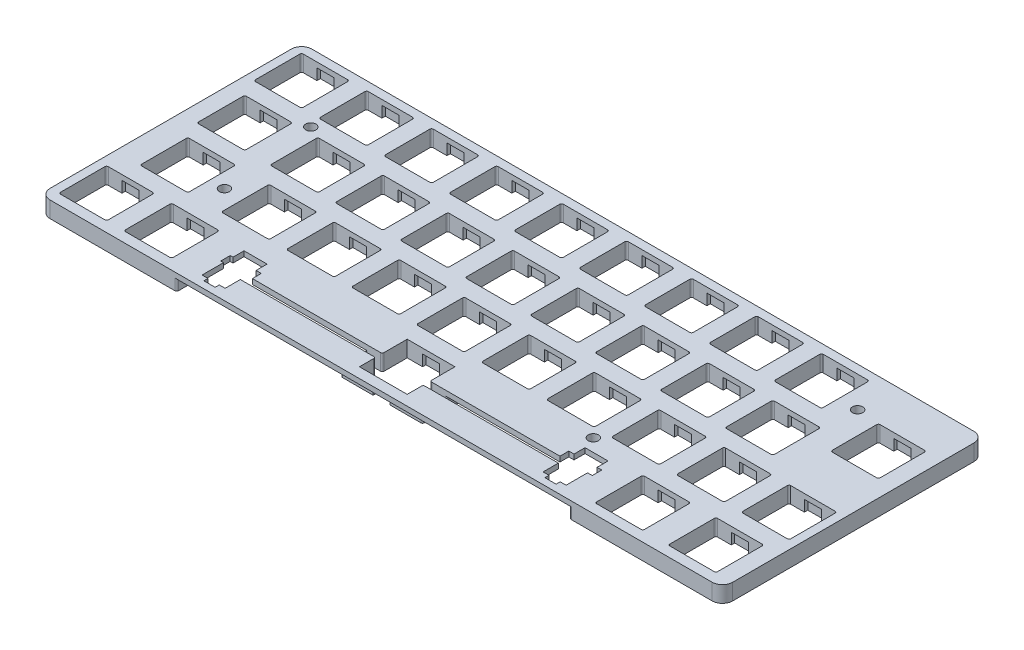
SolidWorks part; units mm, degrees
ref_plane "Front Plane" through (0, 0, 0) normal (0, 0, 1) x (1, 0, 0)
ref_plane "Top Plane" through (0, 0, 0) normal (0, 1, 0) x (1, 0, 0)
ref_plane "Right Plane" through (0, 0, 0) normal (1, 0, 0) x (0, 0, -1)
sketch "Sketch1" plane through (0, 0, 0) normal (0, 1, 0) x (1, 0, 0)
  line L0 (-2.525, 73.675) -> (197.5, 73.675)
  line L1 (-2.525, 73.675) -> (-2.525, -3)
  line L2 (197.5, 73.675) -> (197.5, -3)
  line L3 (-2.525, -3) -> (197.5, -3)
  line L5 (102.1062, 14) -> (88.1063, 14)
  line L6 (102.1062, 0) -> (88.1063, 0)
  line L8 (88.1063, 14) -> (88.1063, 9.3)
  line L9 (88.1063, 9.3) -> (48.5063, 9.3)
  line L10 (48.5063, 9.3) -> (48.5063, 12.53)
  line L11 (48.5063, 12.53) -> (41.7563, 12.53)
  line L12 (41.7563, 12.53) -> (41.7563, 9.3)
  line L13 (41.7563, 9.3) -> (40.9313, 9.3)
  line L14 (40.9313, 9.3) -> (40.9313, 6.515)
  line L15 (40.9313, 6.515) -> (41.7563, 6.515)
  line L16 (41.7563, 6.515) -> (41.7563, 0.23)
  line L17 (41.7563, 0.23) -> (43.4812, 0.23)
  line L18 (43.4812, 0.23) -> (43.4812, -0.97)
  line L19 (43.4812, -0.97) -> (46.7812, -0.97)
  line L20 (46.7812, -0.97) -> (46.7812, 0.23)
  line L21 (46.7812, 0.23) -> (48.5062, 0.23)
  line L22 (48.5062, 0.23) -> (48.5062, 4.7)
  line L23 (48.5062, 4.7) -> (88.1063, 4.7)
  line L24 (88.1063, 4.7) -> (88.1063, 0)
  line L25 (102.1062, 0) -> (102.1062, 4.7)
  line L26 (102.1062, 4.7) -> (141.7063, 4.7)
  line L27 (141.7063, 4.7) -> (141.7063, 0.23)
  line L28 (141.7063, 0.23) -> (143.4313, 0.23)
  line L29 (143.4313, 0.23) -> (143.4313, -0.97)
  line L30 (143.4313, -0.97) -> (146.7313, -0.97)
  line L31 (146.7313, -0.97) -> (146.7313, 0.23)
  line L32 (146.7313, 0.23) -> (148.4563, 0.23)
  line L33 (148.4563, 0.23) -> (148.4563, 6.515)
  line L34 (148.4563, 6.515) -> (149.8378, 6.515)
  line L35 (149.8378, 6.515) -> (149.8378, 9.3)
  line L36 (149.8378, 9.3) -> (148.4563, 9.3)
  line L37 (148.4563, 9.3) -> (148.4563, 12.53)
  line L38 (148.4563, 12.53) -> (141.7063, 12.53)
  line L39 (141.7063, 12.53) -> (141.7063, 9.3)
  line L40 (141.7063, 9.3) -> (102.1062, 9.3)
  line L41 (102.1062, 9.3) -> (102.1062, 14)
  line L42 (88.1063, 9.3) -> (88.1063, 6.7)
  line L43 (50.0312, 9.3) -> (140.1813, 9.3)
  line L44 (50.0312, 9.3) -> (50.0312, 6.7)
  line L45 (50.0312, 6.7) -> (140.1813, 6.7)
  line L46 (140.1813, 9.3) -> (140.1813, 6.7)
  line L47 (102.1062, 9.3) -> (102.1062, 6.7)
  point P0 (0, 64.15)
  line B0 (13.5, 71.15) -> (0.5, 71.15)
  line B1 (194.975, 19.55) -> (194.975, 32.55)
  line B2 (88.6062, 0) -> (101.6062, 0)
  line B3 (101.6062, 14) -> (88.6062, 14)
  line B4 (0.5, 57.15) -> (13.5, 57.15)
  line B5 (14, 57.65) -> (14, 70.65)
  line B6 (0, 70.65) -> (0, 57.65)
  line B7 (19.55, 57.15) -> (32.55, 57.15)
  line B8 (32.55, 71.15) -> (19.55, 71.15)
  line B9 (33.05, 57.65) -> (33.05, 70.65)
  line B10 (19.05, 70.65) -> (19.05, 57.65)
  line B11 (38.6, 57.15) -> (51.6, 57.15)
  line B12 (51.6, 71.15) -> (38.6, 71.15)
  line B13 (52.1, 57.65) -> (52.1, 70.65)
  line B14 (38.1, 70.65) -> (38.1, 57.65)
  line B15 (57.65, 57.15) -> (70.65, 57.15)
  line B16 (70.65, 71.15) -> (57.65, 71.15)
  line B17 (71.15, 57.65) -> (71.15, 70.65)
  line B18 (57.15, 70.65) -> (57.15, 57.65)
  line B19 (76.7, 57.15) -> (89.7, 57.15)
  line B20 (89.7, 71.15) -> (76.7, 71.15)
  line B21 (90.2, 57.65) -> (90.2, 70.65)
  line B22 (76.2, 70.65) -> (76.2, 57.65)
  line B23 (95.75, 57.15) -> (108.75, 57.15)
  line B24 (108.75, 71.15) -> (95.75, 71.15)
  line B25 (109.25, 57.65) -> (109.25, 70.65)
  line B26 (95.25, 70.65) -> (95.25, 57.65)
  line B27 (114.8, 57.15) -> (127.8, 57.15)
  line B28 (127.8, 71.15) -> (114.8, 71.15)
  line B29 (128.3, 57.65) -> (128.3, 70.65)
  line B30 (114.3, 70.65) -> (114.3, 57.65)
  line B31 (133.85, 57.15) -> (146.85, 57.15)
  line B32 (146.85, 71.15) -> (133.85, 71.15)
  line B33 (147.35, 57.65) -> (147.35, 70.65)
  line B34 (133.35, 70.65) -> (133.35, 57.65)
  line B35 (152.9, 57.15) -> (165.9, 57.15)
  line B36 (165.9, 71.15) -> (152.9, 71.15)
  line B37 (166.4, 57.65) -> (166.4, 70.65)
  line B38 (152.4, 70.65) -> (152.4, 57.65)
  line B39 (179.0938, 47.625) -> (192.0938, 47.625)
  line B40 (192.0938, 61.625) -> (179.0938, 61.625)
  line B41 (192.5938, 48.125) -> (192.5938, 61.125)
  line B42 (178.5938, 61.125) -> (178.5938, 48.125)
  line B43 (2.8813, 38.1) -> (15.8812, 38.1)
  line B44 (15.8812, 52.1) -> (2.8813, 52.1)
  line B45 (16.3813, 38.6) -> (16.3813, 51.6)
  line B46 (2.3813, 51.6) -> (2.3813, 38.6)
  line B47 (24.3125, 38.1) -> (37.3125, 38.1)
  line B48 (37.3125, 52.1) -> (24.3125, 52.1)
  line B49 (37.8125, 38.6) -> (37.8125, 51.6)
  line B50 (23.8125, 51.6) -> (23.8125, 38.6)
  line B51 (43.3625, 38.1) -> (56.3625, 38.1)
  line B52 (56.3625, 52.1) -> (43.3625, 52.1)
  line B53 (56.8625, 38.6) -> (56.8625, 51.6)
  line B54 (42.8625, 51.6) -> (42.8625, 38.6)
  line B55 (62.4125, 38.1) -> (75.4125, 38.1)
  line B56 (75.4125, 52.1) -> (62.4125, 52.1)
  line B57 (75.9125, 38.6) -> (75.9125, 51.6)
  line B58 (61.9125, 51.6) -> (61.9125, 38.6)
  line B59 (81.4625, 38.1) -> (94.4625, 38.1)
  line B60 (94.4625, 52.1) -> (81.4625, 52.1)
  line B61 (94.9625, 38.6) -> (94.9625, 51.6)
  line B62 (80.9625, 51.6) -> (80.9625, 38.6)
  line B63 (100.5125, 38.1) -> (113.5125, 38.1)
  line B64 (113.5125, 52.1) -> (100.5125, 52.1)
  line B65 (114.0125, 38.6) -> (114.0125, 51.6)
  line B66 (100.0125, 51.6) -> (100.0125, 38.6)
  line B67 (119.5625, 38.1) -> (132.5625, 38.1)
  line B68 (132.5625, 52.1) -> (119.5625, 52.1)
  line B69 (133.0625, 38.6) -> (133.0625, 51.6)
  line B70 (119.0625, 51.6) -> (119.0625, 38.6)
  line B71 (138.6125, 38.1) -> (151.6125, 38.1)
  line B72 (151.6125, 52.1) -> (138.6125, 52.1)
  line B73 (152.1125, 38.6) -> (152.1125, 51.6)
  line B74 (138.1125, 51.6) -> (138.1125, 38.6)
  line B75 (157.6625, 38.1) -> (170.6625, 38.1)
  line B76 (170.6625, 52.1) -> (157.6625, 52.1)
  line B77 (171.1625, 38.6) -> (171.1625, 51.6)
  line B78 (157.1625, 51.6) -> (157.1625, 38.6)
  line B79 (5.2625, 19.05) -> (18.2625, 19.05)
  line B80 (18.2625, 33.05) -> (5.2625, 33.05)
  line B81 (18.7625, 19.55) -> (18.7625, 32.55)
  line B82 (4.7625, 32.55) -> (4.7625, 19.55)
  line B83 (29.075, 19.05) -> (42.075, 19.05)
  line B84 (42.075, 33.05) -> (29.075, 33.05)
  line B85 (42.575, 19.55) -> (42.575, 32.55)
  line B86 (28.575, 32.55) -> (28.575, 19.55)
  line B87 (48.125, 19.05) -> (61.125, 19.05)
  line B88 (61.125, 33.05) -> (48.125, 33.05)
  line B89 (61.625, 19.55) -> (61.625, 32.55)
  line B90 (47.625, 32.55) -> (47.625, 19.55)
  line B91 (67.175, 19.05) -> (80.175, 19.05)
  line B92 (80.175, 33.05) -> (67.175, 33.05)
  line B93 (80.675, 19.55) -> (80.675, 32.55)
  line B94 (66.675, 32.55) -> (66.675, 19.55)
  line B95 (86.225, 19.05) -> (99.225, 19.05)
  line B96 (99.225, 33.05) -> (86.225, 33.05)
  line B97 (99.725, 19.55) -> (99.725, 32.55)
  line B98 (85.725, 32.55) -> (85.725, 19.55)
  line B99 (105.275, 19.05) -> (118.275, 19.05)
  line B100 (118.275, 33.05) -> (105.275, 33.05)
  line B101 (118.775, 19.55) -> (118.775, 32.55)
  line B102 (104.775, 32.55) -> (104.775, 19.55)
  line B103 (124.325, 19.05) -> (137.325, 19.05)
  line B104 (137.325, 33.05) -> (124.325, 33.05)
  line B105 (137.825, 19.55) -> (137.825, 32.55)
  line B106 (123.825, 32.55) -> (123.825, 19.55)
  line B107 (143.375, 19.05) -> (156.375, 19.05)
  line B108 (156.375, 33.05) -> (143.375, 33.05)
  line B109 (156.875, 19.55) -> (156.875, 32.55)
  line B110 (142.875, 32.55) -> (142.875, 19.55)
  line B111 (162.425, 19.05) -> (175.425, 19.05)
  line B112 (175.425, 33.05) -> (162.425, 33.05)
  line B113 (175.925, 19.55) -> (175.925, 32.55)
  line B114 (161.925, 32.55) -> (161.925, 19.55)
  line B115 (181.475, 19.05) -> (194.475, 19.05)
  line B116 (194.475, 33.05) -> (181.475, 33.05)
  line B117 (180.975, 32.55) -> (180.975, 19.55)
  line B118 (0.5, 0) -> (13.5, 0)
  line B119 (13.5, 14) -> (0.5, 14)
  line B120 (14, 0.5) -> (14, 13.5)
  line B121 (0, 13.5) -> (0, 0.5)
  line B122 (19.55, 0) -> (32.55, 0)
  line B123 (32.55, 14) -> (19.55, 14)
  line B124 (33.05, 0.5) -> (33.05, 13.5)
  line B125 (19.05, 13.5) -> (19.05, 0.5)
  line B126 (102.1062, 0.5) -> (102.1062, 13.5)
  line B127 (88.1063, 13.5) -> (88.1063, 0.5)
  line B128 (157.6625, 0) -> (170.6625, 0)
  line B129 (170.6625, 14) -> (157.6625, 14)
  line B130 (171.1625, 0.5) -> (171.1625, 13.5)
  line B131 (157.1625, 13.5) -> (157.1625, 0.5)
  line B132 (179.0938, 0) -> (192.0938, 0)
  line B133 (192.0938, 14) -> (179.0938, 14)
  line B134 (192.5938, 0.5) -> (192.5938, 13.5)
  line B135 (178.5938, 13.5) -> (178.5938, 0.5)
  arc B136 (0, 57.65) -> (0.5, 57.15) centre (0.5, 57.65) ccw
  arc B137 (13.5, 57.15) -> (14, 57.65) centre (13.5, 57.65) ccw
  arc B138 (14, 70.65) -> (13.5, 71.15) centre (13.5, 70.65) ccw
  arc B139 (0.5, 71.15) -> (0, 70.65) centre (0.5, 70.65) ccw
  arc B140 (19.05, 57.65) -> (19.55, 57.15) centre (19.55, 57.65) ccw
  arc B141 (32.55, 57.15) -> (33.05, 57.65) centre (32.55, 57.65) ccw
  arc B142 (33.05, 70.65) -> (32.55, 71.15) centre (32.55, 70.65) ccw
  arc B143 (19.55, 71.15) -> (19.05, 70.65) centre (19.55, 70.65) ccw
  arc B144 (38.1, 57.65) -> (38.6, 57.15) centre (38.6, 57.65) ccw
  arc B145 (51.6, 57.15) -> (52.1, 57.65) centre (51.6, 57.65) ccw
  arc B146 (52.1, 70.65) -> (51.6, 71.15) centre (51.6, 70.65) ccw
  arc B147 (38.6, 71.15) -> (38.1, 70.65) centre (38.6, 70.65) ccw
  arc B148 (57.15, 57.65) -> (57.65, 57.15) centre (57.65, 57.65) ccw
  arc B149 (70.65, 57.15) -> (71.15, 57.65) centre (70.65, 57.65) ccw
  arc B150 (71.15, 70.65) -> (70.65, 71.15) centre (70.65, 70.65) ccw
  arc B151 (57.65, 71.15) -> (57.15, 70.65) centre (57.65, 70.65) ccw
  arc B152 (76.2, 57.65) -> (76.7, 57.15) centre (76.7, 57.65) ccw
  arc B153 (89.7, 57.15) -> (90.2, 57.65) centre (89.7, 57.65) ccw
  arc B154 (90.2, 70.65) -> (89.7, 71.15) centre (89.7, 70.65) ccw
  arc B155 (76.7, 71.15) -> (76.2, 70.65) centre (76.7, 70.65) ccw
  arc B156 (95.25, 57.65) -> (95.75, 57.15) centre (95.75, 57.65) ccw
  arc B157 (108.75, 57.15) -> (109.25, 57.65) centre (108.75, 57.65) ccw
  arc B158 (109.25, 70.65) -> (108.75, 71.15) centre (108.75, 70.65) ccw
  arc B159 (95.75, 71.15) -> (95.25, 70.65) centre (95.75, 70.65) ccw
  arc B160 (114.3, 57.65) -> (114.8, 57.15) centre (114.8, 57.65) ccw
  arc B161 (127.8, 57.15) -> (128.3, 57.65) centre (127.8, 57.65) ccw
  arc B162 (128.3, 70.65) -> (127.8, 71.15) centre (127.8, 70.65) ccw
  arc B163 (114.8, 71.15) -> (114.3, 70.65) centre (114.8, 70.65) ccw
  arc B164 (133.35, 57.65) -> (133.85, 57.15) centre (133.85, 57.65) ccw
  arc B165 (146.85, 57.15) -> (147.35, 57.65) centre (146.85, 57.65) ccw
  arc B166 (147.35, 70.65) -> (146.85, 71.15) centre (146.85, 70.65) ccw
  arc B167 (133.85, 71.15) -> (133.35, 70.65) centre (133.85, 70.65) ccw
  arc B168 (152.4, 57.65) -> (152.9, 57.15) centre (152.9, 57.65) ccw
  arc B169 (165.9, 57.15) -> (166.4, 57.65) centre (165.9, 57.65) ccw
  arc B170 (166.4, 70.65) -> (165.9, 71.15) centre (165.9, 70.65) ccw
  arc B171 (152.9, 71.15) -> (152.4, 70.65) centre (152.9, 70.65) ccw
  arc B172 (178.5938, 48.125) -> (179.0938, 47.625) centre (179.0938, 48.125) ccw
  arc B173 (192.0938, 47.625) -> (192.5938, 48.125) centre (192.0938, 48.125) ccw
  arc B174 (192.5938, 61.125) -> (192.0938, 61.625) centre (192.0938, 61.125) ccw
  arc B175 (179.0938, 61.625) -> (178.5938, 61.125) centre (179.0938, 61.125) ccw
  arc B176 (2.3813, 38.6) -> (2.8813, 38.1) centre (2.8813, 38.6) ccw
  arc B177 (15.8812, 38.1) -> (16.3813, 38.6) centre (15.8812, 38.6) ccw
  arc B178 (16.3813, 51.6) -> (15.8812, 52.1) centre (15.8812, 51.6) ccw
  arc B179 (2.8813, 52.1) -> (2.3813, 51.6) centre (2.8813, 51.6) ccw
  arc B180 (23.8125, 38.6) -> (24.3125, 38.1) centre (24.3125, 38.6) ccw
  arc B181 (37.3125, 38.1) -> (37.8125, 38.6) centre (37.3125, 38.6) ccw
  arc B182 (37.8125, 51.6) -> (37.3125, 52.1) centre (37.3125, 51.6) ccw
  arc B183 (24.3125, 52.1) -> (23.8125, 51.6) centre (24.3125, 51.6) ccw
  arc B184 (42.8625, 38.6) -> (43.3625, 38.1) centre (43.3625, 38.6) ccw
  arc B185 (56.3625, 38.1) -> (56.8625, 38.6) centre (56.3625, 38.6) ccw
  arc B186 (56.8625, 51.6) -> (56.3625, 52.1) centre (56.3625, 51.6) ccw
  arc B187 (43.3625, 52.1) -> (42.8625, 51.6) centre (43.3625, 51.6) ccw
  arc B188 (61.9125, 38.6) -> (62.4125, 38.1) centre (62.4125, 38.6) ccw
  arc B189 (75.4125, 38.1) -> (75.9125, 38.6) centre (75.4125, 38.6) ccw
  arc B190 (75.9125, 51.6) -> (75.4125, 52.1) centre (75.4125, 51.6) ccw
  arc B191 (62.4125, 52.1) -> (61.9125, 51.6) centre (62.4125, 51.6) ccw
  arc B192 (80.9625, 38.6) -> (81.4625, 38.1) centre (81.4625, 38.6) ccw
  arc B193 (94.4625, 38.1) -> (94.9625, 38.6) centre (94.4625, 38.6) ccw
  arc B194 (94.9625, 51.6) -> (94.4625, 52.1) centre (94.4625, 51.6) ccw
  arc B195 (81.4625, 52.1) -> (80.9625, 51.6) centre (81.4625, 51.6) ccw
  arc B196 (100.0125, 38.6) -> (100.5125, 38.1) centre (100.5125, 38.6) ccw
  arc B197 (113.5125, 38.1) -> (114.0125, 38.6) centre (113.5125, 38.6) ccw
  arc B198 (114.0125, 51.6) -> (113.5125, 52.1) centre (113.5125, 51.6) ccw
  arc B199 (100.5125, 52.1) -> (100.0125, 51.6) centre (100.5125, 51.6) ccw
  arc B200 (119.0625, 38.6) -> (119.5625, 38.1) centre (119.5625, 38.6) ccw
  arc B201 (132.5625, 38.1) -> (133.0625, 38.6) centre (132.5625, 38.6) ccw
  arc B202 (133.0625, 51.6) -> (132.5625, 52.1) centre (132.5625, 51.6) ccw
  arc B203 (119.5625, 52.1) -> (119.0625, 51.6) centre (119.5625, 51.6) ccw
  arc B204 (138.1125, 38.6) -> (138.6125, 38.1) centre (138.6125, 38.6) ccw
  arc B205 (151.6125, 38.1) -> (152.1125, 38.6) centre (151.6125, 38.6) ccw
  arc B206 (152.1125, 51.6) -> (151.6125, 52.1) centre (151.6125, 51.6) ccw
  arc B207 (138.6125, 52.1) -> (138.1125, 51.6) centre (138.6125, 51.6) ccw
  arc B208 (157.1625, 38.6) -> (157.6625, 38.1) centre (157.6625, 38.6) ccw
  arc B209 (170.6625, 38.1) -> (171.1625, 38.6) centre (170.6625, 38.6) ccw
  arc B210 (171.1625, 51.6) -> (170.6625, 52.1) centre (170.6625, 51.6) ccw
  arc B211 (157.6625, 52.1) -> (157.1625, 51.6) centre (157.6625, 51.6) ccw
  arc B212 (4.7625, 19.55) -> (5.2625, 19.05) centre (5.2625, 19.55) ccw
  arc B213 (18.2625, 19.05) -> (18.7625, 19.55) centre (18.2625, 19.55) ccw
  arc B214 (18.7625, 32.55) -> (18.2625, 33.05) centre (18.2625, 32.55) ccw
  arc B215 (5.2625, 33.05) -> (4.7625, 32.55) centre (5.2625, 32.55) ccw
  arc B216 (28.575, 19.55) -> (29.075, 19.05) centre (29.075, 19.55) ccw
  arc B217 (42.075, 19.05) -> (42.575, 19.55) centre (42.075, 19.55) ccw
  arc B218 (42.575, 32.55) -> (42.075, 33.05) centre (42.075, 32.55) ccw
  arc B219 (29.075, 33.05) -> (28.575, 32.55) centre (29.075, 32.55) ccw
  arc B220 (47.625, 19.55) -> (48.125, 19.05) centre (48.125, 19.55) ccw
  arc B221 (61.125, 19.05) -> (61.625, 19.55) centre (61.125, 19.55) ccw
  arc B222 (61.625, 32.55) -> (61.125, 33.05) centre (61.125, 32.55) ccw
  arc B223 (48.125, 33.05) -> (47.625, 32.55) centre (48.125, 32.55) ccw
  arc B224 (66.675, 19.55) -> (67.175, 19.05) centre (67.175, 19.55) ccw
  arc B225 (80.175, 19.05) -> (80.675, 19.55) centre (80.175, 19.55) ccw
  arc B226 (80.675, 32.55) -> (80.175, 33.05) centre (80.175, 32.55) ccw
  arc B227 (67.175, 33.05) -> (66.675, 32.55) centre (67.175, 32.55) ccw
  arc B228 (85.725, 19.55) -> (86.225, 19.05) centre (86.225, 19.55) ccw
  arc B229 (99.225, 19.05) -> (99.725, 19.55) centre (99.225, 19.55) ccw
  arc B230 (99.725, 32.55) -> (99.225, 33.05) centre (99.225, 32.55) ccw
  arc B231 (86.225, 33.05) -> (85.725, 32.55) centre (86.225, 32.55) ccw
  arc B232 (104.775, 19.55) -> (105.275, 19.05) centre (105.275, 19.55) ccw
  arc B233 (118.275, 19.05) -> (118.775, 19.55) centre (118.275, 19.55) ccw
  arc B234 (118.775, 32.55) -> (118.275, 33.05) centre (118.275, 32.55) ccw
  arc B235 (105.275, 33.05) -> (104.775, 32.55) centre (105.275, 32.55) ccw
  arc B236 (123.825, 19.55) -> (124.325, 19.05) centre (124.325, 19.55) ccw
  arc B237 (137.325, 19.05) -> (137.825, 19.55) centre (137.325, 19.55) ccw
  arc B238 (137.825, 32.55) -> (137.325, 33.05) centre (137.325, 32.55) ccw
  arc B239 (124.325, 33.05) -> (123.825, 32.55) centre (124.325, 32.55) ccw
  arc B240 (142.875, 19.55) -> (143.375, 19.05) centre (143.375, 19.55) ccw
  arc B241 (156.375, 19.05) -> (156.875, 19.55) centre (156.375, 19.55) ccw
  arc B242 (156.875, 32.55) -> (156.375, 33.05) centre (156.375, 32.55) ccw
  arc B243 (143.375, 33.05) -> (142.875, 32.55) centre (143.375, 32.55) ccw
  arc B244 (161.925, 19.55) -> (162.425, 19.05) centre (162.425, 19.55) ccw
  arc B245 (175.425, 19.05) -> (175.925, 19.55) centre (175.425, 19.55) ccw
  arc B246 (175.925, 32.55) -> (175.425, 33.05) centre (175.425, 32.55) ccw
  arc B247 (162.425, 33.05) -> (161.925, 32.55) centre (162.425, 32.55) ccw
  arc B248 (180.975, 19.55) -> (181.475, 19.05) centre (181.475, 19.55) ccw
  arc B249 (194.475, 19.05) -> (194.975, 19.55) centre (194.475, 19.55) ccw
  arc B250 (194.975, 32.55) -> (194.475, 33.05) centre (194.475, 32.55) ccw
  arc B251 (181.475, 33.05) -> (180.975, 32.55) centre (181.475, 32.55) ccw
  arc B252 (0, 0.5) -> (0.5, 0) centre (0.5, 0.5) ccw
  arc B253 (13.5, 0) -> (14, 0.5) centre (13.5, 0.5) ccw
  arc B254 (14, 13.5) -> (13.5, 14) centre (13.5, 13.5) ccw
  arc B255 (0.5, 14) -> (0, 13.5) centre (0.5, 13.5) ccw
  arc B256 (19.05, 0.5) -> (19.55, 0) centre (19.55, 0.5) ccw
  arc B257 (32.55, 0) -> (33.05, 0.5) centre (32.55, 0.5) ccw
  arc B258 (33.05, 13.5) -> (32.55, 14) centre (32.55, 13.5) ccw
  arc B259 (19.55, 14) -> (19.05, 13.5) centre (19.55, 13.5) ccw
  arc B260 (88.1063, 0.5) -> (88.6062, 0) centre (88.6062, 0.5) ccw
  arc B261 (101.6062, 0) -> (102.1062, 0.5) centre (101.6062, 0.5) ccw
  arc B262 (102.1062, 13.5) -> (101.6062, 14) centre (101.6062, 13.5) ccw
  arc B263 (88.6062, 14) -> (88.1063, 13.5) centre (88.6062, 13.5) ccw
  arc B264 (157.1625, 0.5) -> (157.6625, 0) centre (157.6625, 0.5) ccw
  arc B265 (170.6625, 0) -> (171.1625, 0.5) centre (170.6625, 0.5) ccw
  arc B266 (171.1625, 13.5) -> (170.6625, 14) centre (170.6625, 13.5) ccw
  arc B267 (157.6625, 14) -> (157.1625, 13.5) centre (157.6625, 13.5) ccw
  arc B268 (178.5938, 0.5) -> (179.0938, 0) centre (179.0938, 0.5) ccw
  arc B269 (192.0938, 0) -> (192.5938, 0.5) centre (192.0938, 0.5) ccw
  arc B270 (192.5938, 13.5) -> (192.0938, 14) centre (192.0938, 13.5) ccw
  arc B271 (179.0938, 14) -> (178.5938, 13.5) centre (179.0938, 13.5) ccw
  dimension "D1" = 2.525
  dimension "D2" = 2.525
  dimension "D3" = 2.525
  dimension "D4" = 3
  dimension "D5" = 14
  dimension "D6" = 39.6
  dimension "D7" = 3.23
  dimension "D8" = 4.7
  dimension "D9" = 6.75
  dimension "D10" = 3.23
  dimension "D11" = 0.825
  dimension "D12" = 2.785
  dimension "D13" = 0.825
  dimension "D14" = 6.285
  dimension "D15" = 1.725
  dimension "D16" = 1.2
  dimension "D17" = 3.3
  dimension "D18" = 1.2
  dimension "D19" = 1.725
  dimension "D20" = 4.47
  dimension "D21" = 4.7
  dimension "D22" = 14
  dimension "D23" = 6.75
  dimension "D24" = 3.3
  dimension "D25" = 1.725
  dimension "D26" = 1.725
  dimension "D27" = 39.6
  dimension "D28" = 39.6
  dimension "D29" = 2
  dimension "D30" = 1.525
  dimension "D31" = 1.525
sketch_block_instance "kbplate (1)-1"
sketch_block "kbplate (1)"
extrude "Boss-Extrude1" add sketch "Sketch1" along normal blind 4.75 contours L1 L3 L2 L0 B271 B133 B270 B134 B269 B132 B268 B135 B267 B129 B266 B130 B265 B128 B264 B131 B259 B123 B258 B124 B257 B122 B256 B125 B255 B119 B254 B120 B253 B118 B252 B121 B251 B116 B250 B1 B249 B115 B248 B117 B247 | L44 L45 L42 L9 | L40 L47 L45 L46 region at (99.9288, 0, -34.0795) region at (121.1438, 0, -8) region at (69.0688, 0, -8)
fillet "Fillet1" radius 3 4 edges at (-2.525, 2.375, 3) (197.5, 2.375, 3) (197.5, 2.375, -73.675) (-2.525, 2.375, -73.675)
sketch "Sketch4" plane through (0, 0, 0) normal (0, -1, 0) x (1, 0, 0)
  line L0 (102.1062, -14) -> (88.1063, -14) construction
  line L1 (0, -16) -> (192.5938, -16)
  line L2 (0, -16) -> (0, 8.776)
  line L3 (0, 8.776) -> (192.5938, 8.776)
  line L4 (192.5938, -16) -> (192.5938, 8.776)
  line L5 (14, -0.5) -> (14, -13.5) construction
  line L6 (178.5938, -13.5) -> (178.5938, -0.5) construction
  line L8 (83.1062, 0.475) -> (107.1063, 0.475)
  line L9 (83.1062, 0.475) -> (83.1062, -16)
  line L10 (83.1062, -16) -> (107.1063, -16)
  line L11 (107.1063, 0.475) -> (107.1063, -16)
  line L12 (88.1063, -4.7) -> (88.1063, 0) construction
  line L13 (102.1062, 0) -> (102.1062, -4.7) construction
  line L15 (0.475, 3) -> (194.5, 3) construction
  line L16 (33.05, -0.5) -> (33.05, -13.5) construction
  line L17 (0, 4.2546) -> (37.55, 4.2546)
  line L18 (0, 4.2546) -> (0, -16)
  line L19 (0, -16) -> (37.55, -16)
  line L20 (37.55, 4.2546) -> (37.55, -16)
  line L23 (157.1625, -13.5) -> (157.1625, -0.5) construction
  line L24 (152.6625, 3) -> (192.5938, 3)
  line L25 (152.6625, 3) -> (152.6625, -16)
  line L26 (152.6625, -16) -> (192.5938, -16)
  line L27 (192.5938, 3) -> (192.5938, -16)
  dimension "D1" = 2
  dimension "D2" = 14
  dimension "D3" = 14
  dimension "D4" = 5
  dimension "D5" = 5
  dimension "D6" = 2.525
  dimension "D7" = 4.5
  dimension "D8" = 4.5
extrude "Cut-Extrude1" cut sketch "Sketch4" against normal blind 3.25 contours L8 L11 L1 L4 L3 L2 L9 region at (39.4918, 0, -5.8727)
fillet "Fillet2" radius 0.5 16 edges at (88.1063, 2.375, -4.7) (88.1063, 2.375, -6.7) (83.1062, 1.625, -6.7) (83.1062, 1.625, -4.7) (102.1062, 2.375, -4.7) (102.1062, 2.375, -6.7) (107.1063, 1.625, -6.7) (107.1063, 1.625, -4.7) (107.1063, 1.625, -16) (83.1062, 1.625, -16) (107.1063, 1.625, 0.475) (83.1062, 1.625, 0.475) (152.6625, 1.625, 3) (152.6625, 1.625, -16) (37.55, 1.625, 3) (37.55, 1.625, -16)
sketch "Sketch5" plane through (0, 4.75, 0) normal (0, 1, 0) x (1, 0, 0)
  line L0 (13.5, 71.15) -> (0.5, 71.15) construction
  line L1 (4.5, 72.15) -> (9.5, 72.15)
  line L2 (4.5, 72.15) -> (4.5, 56.15)
  line L3 (4.5, 56.15) -> (9.5, 56.15)
  line L4 (9.5, 72.15) -> (9.5, 56.15)
  line L5 (0.5, 57.15) -> (13.5, 57.15) construction
  line L6 (0, 70.65) -> (0, 57.65) construction
  line L7 (23.55, 72.15) -> (28.55, 72.15)
  line L8 (28.55, 72.15) -> (28.55, 56.15)
  line L9 (23.55, 56.15) -> (28.55, 56.15)
  line L10 (23.55, 72.15) -> (23.55, 56.15)
  line L11 (42.6, 72.15) -> (47.6, 72.15)
  line L12 (47.6, 72.15) -> (47.6, 56.15)
  line L13 (42.6, 56.15) -> (47.6, 56.15)
  line L14 (42.6, 72.15) -> (42.6, 56.15)
  line L15 (61.65, 72.15) -> (66.65, 72.15)
  line L16 (66.65, 72.15) -> (66.65, 56.15)
  line L17 (61.65, 56.15) -> (66.65, 56.15)
  line L18 (61.65, 72.15) -> (61.65, 56.15)
  line L19 (80.7, 72.15) -> (85.7, 72.15)
  line L20 (85.7, 72.15) -> (85.7, 56.15)
  line L21 (80.7, 56.15) -> (85.7, 56.15)
  line L22 (80.7, 72.15) -> (80.7, 56.15)
  line L23 (99.75, 72.15) -> (104.75, 72.15)
  line L24 (104.75, 72.15) -> (104.75, 56.15)
  line L25 (99.75, 56.15) -> (104.75, 56.15)
  line L26 (99.75, 72.15) -> (99.75, 56.15)
  line L27 (118.8, 72.15) -> (123.8, 72.15)
  line L28 (123.8, 72.15) -> (123.8, 56.15)
  line L29 (118.8, 56.15) -> (123.8, 56.15)
  line L30 (118.8, 72.15) -> (118.8, 56.15)
  line L31 (137.85, 72.15) -> (142.85, 72.15)
  line L32 (142.85, 72.15) -> (142.85, 56.15)
  line L33 (137.85, 56.15) -> (142.85, 56.15)
  line L34 (137.85, 72.15) -> (137.85, 56.15)
  line L35 (156.9, 72.15) -> (161.9, 72.15)
  line L36 (161.9, 72.15) -> (161.9, 56.15)
  line L37 (156.9, 56.15) -> (161.9, 56.15)
  line L38 (156.9, 72.15) -> (156.9, 56.15)
  line L39 (37.3125, 52.1) -> (24.3125, 52.1) construction
  line L40 (28.3125, 53.1) -> (33.3125, 53.1)
  line L41 (28.3125, 53.1) -> (28.3125, 37.1)
  line L42 (28.3125, 37.1) -> (33.3125, 37.1)
  line L43 (33.3125, 53.1) -> (33.3125, 37.1)
  line L44 (24.3125, 38.1) -> (37.3125, 38.1) construction
  line L45 (23.8125, 51.6) -> (23.8125, 38.6) construction
  line L46 (47.3625, 53.1) -> (52.3625, 53.1)
  line L47 (52.3625, 53.1) -> (52.3625, 37.1)
  line L48 (47.3625, 37.1) -> (52.3625, 37.1)
  line L49 (47.3625, 53.1) -> (47.3625, 37.1)
  line L50 (66.4125, 53.1) -> (71.4125, 53.1)
  line L51 (71.4125, 53.1) -> (71.4125, 37.1)
  line L52 (66.4125, 37.1) -> (71.4125, 37.1)
  line L53 (66.4125, 53.1) -> (66.4125, 37.1)
  line L54 (85.4625, 53.1) -> (90.4625, 53.1)
  line L55 (90.4625, 53.1) -> (90.4625, 37.1)
  line L56 (85.4625, 37.1) -> (90.4625, 37.1)
  line L57 (85.4625, 53.1) -> (85.4625, 37.1)
  line L58 (104.5125, 53.1) -> (109.5125, 53.1)
  line L59 (109.5125, 53.1) -> (109.5125, 37.1)
  line L60 (104.5125, 37.1) -> (109.5125, 37.1)
  line L61 (104.5125, 53.1) -> (104.5125, 37.1)
  line L62 (123.5625, 53.1) -> (128.5625, 53.1)
  line L63 (128.5625, 53.1) -> (128.5625, 37.1)
  line L64 (123.5625, 37.1) -> (128.5625, 37.1)
  line L65 (123.5625, 53.1) -> (123.5625, 37.1)
  line L66 (142.6125, 53.1) -> (147.6125, 53.1)
  line L67 (147.6125, 53.1) -> (147.6125, 37.1)
  line L68 (142.6125, 37.1) -> (147.6125, 37.1)
  line L69 (142.6125, 53.1) -> (142.6125, 37.1)
  line L70 (161.6625, 53.1) -> (166.6625, 53.1)
  line L71 (166.6625, 53.1) -> (166.6625, 37.1)
  line L72 (161.6625, 37.1) -> (166.6625, 37.1)
  line L73 (161.6625, 53.1) -> (161.6625, 37.1)
  line L74 (42.075, 33.05) -> (29.075, 33.05) construction
  line L75 (33.075, 34.05) -> (38.075, 34.05)
  line L76 (33.075, 34.05) -> (33.075, 18.05)
  line L77 (33.075, 18.05) -> (38.075, 18.05)
  line L78 (38.075, 34.05) -> (38.075, 18.05)
  line L79 (29.075, 19.05) -> (42.075, 19.05) construction
  line L80 (28.575, 32.55) -> (28.575, 19.55) construction
  line L81 (52.125, 34.05) -> (57.125, 34.05)
  line L82 (57.125, 34.05) -> (57.125, 18.05)
  line L83 (52.125, 34.05) -> (52.125, 18.05)
  line L84 (52.125, 18.05) -> (57.125, 18.05)
  line L85 (71.175, 34.05) -> (76.175, 34.05)
  line L86 (76.175, 34.05) -> (76.175, 18.05)
  line L87 (71.175, 34.05) -> (71.175, 18.05)
  line L88 (71.175, 18.05) -> (76.175, 18.05)
  line L89 (90.225, 34.05) -> (95.225, 34.05)
  line L90 (95.225, 34.05) -> (95.225, 18.05)
  line L91 (90.225, 34.05) -> (90.225, 18.05)
  line L92 (90.225, 18.05) -> (95.225, 18.05)
  line L93 (109.275, 34.05) -> (114.275, 34.05)
  line L94 (114.275, 34.05) -> (114.275, 18.05)
  line L95 (109.275, 34.05) -> (109.275, 18.05)
  line L96 (109.275, 18.05) -> (114.275, 18.05)
  line L97 (128.325, 34.05) -> (133.325, 34.05)
  line L98 (133.325, 34.05) -> (133.325, 18.05)
  line L99 (128.325, 34.05) -> (128.325, 18.05)
  line L100 (128.325, 18.05) -> (133.325, 18.05)
  line L101 (147.375, 34.05) -> (152.375, 34.05)
  line L102 (152.375, 34.05) -> (152.375, 18.05)
  line L103 (147.375, 34.05) -> (147.375, 18.05)
  line L104 (147.375, 18.05) -> (152.375, 18.05)
  line L105 (166.425, 34.05) -> (171.425, 34.05)
  line L106 (171.425, 34.05) -> (171.425, 18.05)
  line L107 (166.425, 34.05) -> (166.425, 18.05)
  line L108 (166.425, 18.05) -> (171.425, 18.05)
  line L109 (185.475, 34.05) -> (190.475, 34.05)
  line L110 (190.475, 34.05) -> (190.475, 18.05)
  line L111 (185.475, 34.05) -> (185.475, 18.05)
  line L112 (185.475, 18.05) -> (190.475, 18.05)
  line L113 (15.8812, 52.1) -> (2.8813, 52.1) construction
  line L114 (6.8813, 53.1) -> (11.8812, 53.1)
  line L115 (6.8813, 53.1) -> (6.8813, 37.1)
  line L116 (6.8813, 37.1) -> (11.8813, 37.1)
  line L117 (11.8812, 53.1) -> (11.8813, 37.1)
  line L118 (9.2625, 34.05) -> (14.2625, 34.05)
  line L119 (9.2625, 34.05) -> (9.2625, 18.05)
  line L120 (9.2625, 18.05) -> (14.2625, 18.05)
  line L121 (14.2625, 34.05) -> (14.2625, 18.05)
  line L122 (183.0938, 62.625) -> (188.0938, 62.625)
  line L123 (183.0938, 62.625) -> (183.0938, 46.625)
  line L124 (183.0938, 46.625) -> (188.0938, 46.625)
  line L125 (188.0938, 62.625) -> (188.0938, 46.625)
  line L126 (2.8813, 38.1) -> (15.8812, 38.1) construction
  line L127 (2.3813, 51.6) -> (2.3813, 38.6) construction
  line L128 (5.2625, 19.05) -> (18.2625, 19.05) construction
  line L129 (18.2625, 33.05) -> (5.2625, 33.05) construction
  line L130 (4.7625, 32.55) -> (4.7625, 19.55) construction
  line L131 (192.0938, 61.625) -> (179.0938, 61.625) construction
  line L132 (179.0938, 47.625) -> (192.0938, 47.625) construction
  line L133 (178.5938, 61.125) -> (178.5938, 48.125) construction
  line L134 (13.5, 14) -> (0.5, 14) construction
  line L135 (4.5, 15) -> (9.5, 15)
  line L136 (4.5, 15) -> (4.5, -1)
  line L137 (4.5, -1) -> (9.5, -1)
  line L138 (9.5, 15) -> (9.5, -1)
  line L139 (0, 13.5) -> (0, 0.5) construction
  line L140 (23.55, 15) -> (28.55, 15)
  line L141 (28.55, 15) -> (28.55, -1)
  line L142 (23.55, 15) -> (23.55, -1)
  line L143 (23.55, -1) -> (28.55, -1)
  line L144 (170.6625, 14) -> (157.6625, 14) construction
  line L145 (161.6625, 15) -> (166.6625, 15)
  line L146 (161.6625, 15) -> (161.6625, -1)
  line L147 (161.6625, -1) -> (166.6625, -1)
  line L148 (166.6625, 15) -> (166.6625, -1)
  line L149 (157.6625, 0) -> (170.6625, 0) construction
  line L150 (157.1625, 13.5) -> (157.1625, 0.5) construction
  line L151 (0.5, 0) -> (13.5, 0) construction
  line L152 (192.0938, 14) -> (179.0938, 14) construction
  line L153 (183.0938, 15) -> (188.0938, 15)
  line L154 (183.0938, 15) -> (183.0938, -1)
  line L155 (183.0938, -1) -> (188.0938, -1)
  line L156 (188.0938, 15) -> (188.0938, -1)
  line L157 (178.5938, 13.5) -> (178.5938, 0.5) construction
  line L158 (179.0938, 0) -> (192.0938, 0) construction
  line L159 (102.1062, 14) -> (88.1063, 14) construction
  line L160 (92.6063, 15) -> (97.6063, 15)
  line L161 (92.6063, 15) -> (92.6063, -1)
  line L162 (92.6063, -1) -> (97.6063, -1)
  line L163 (97.6063, 15) -> (97.6063, -1)
  line L164 (102.1062, 0) -> (88.1063, 0) construction
  line L165 (88.1063, 14) -> (88.1063, 7.2) construction
  dimension "D1" = 1
  dimension "D2" = 1
  dimension "D3" = 5
  dimension "D4" = 4.5
  dimension "D5" = 9
  dimension "D6" = 1
  dimension "D7" = 1
  dimension "D8" = 5
  dimension "D9" = 4.5
  dimension "D11" = 1
  dimension "D12" = 5
  dimension "D13" = 1
  dimension "D14" = 4.5
  dimension "D16" = 1
  dimension "D17" = 1
  dimension "D18" = 5
  dimension "D19" = 4.5
  dimension "D20" = 1
  dimension "D21" = 1
  dimension "D22" = 5
  dimension "D23" = 4.5
  dimension "D24" = 1
  dimension "D25" = 1
  dimension "D26" = 4.5
  dimension "D27" = 5
  dimension "D28" = 1
  dimension "D29" = 5
  dimension "D30" = 4.5
  dimension "D32" = 1
  dimension "D33" = 1
  dimension "D34" = 5
  dimension "D35" = 4.5
  dimension "D36" = 1
  dimension "D37" = 1
  dimension "D38" = 5
  dimension "D39" = 4.5
  dimension "D40" = 1
  dimension "D41" = 1
  dimension "D42" = 1
  dimension "D43" = 4.5
  dimension "D44" = 5
  dimension "D10" = 8
  dimension "D15" = 9
  dimension "D31" = 2
extrude "Cut-Extrude2" cut sketch "Sketch5" against normal blind 3.25 from offset 1.5 offset against normal yes
sketch "Sketch6" plane through (0, 4.75, 0) normal (0, 1, 0) x (1, 0, 0)
  line L0 (-2.525, 73.675) -> (197.5, 73.675)
  line L1 (197.5, 73.675) -> (197.5, -3)
  line L2 (197.5, -3) -> (-2.525, -3)
  line L3 (-2.525, -3) -> (-2.525, 73.675)
  circle A0 centre (23.1153, 25.4289) radius 1.5
  circle A1 centre (172.0219, 62.0916) radius 1.5
  circle A2 centre (20.1153, 53.7438) radius 1.5
  circle A3 centre (140.3993, 16.2494) radius 1.5
  point P11 (0, 0)
  dimension "D1" = 3
  dimension "D2" = 3
  dimension "D3" = 3
  dimension "D4" = 3
extrude "Cut-Extrude3" cut sketch "Sketch6" against normal through all contours A2 | A0 | A1 | A3 region at (23.1153, 4.75, -25.4289) region at (172.0219, 4.75, -62.0916) region at (20.1153, 4.75, -53.7438) region at (140.3993, 4.75, -16.2494)
